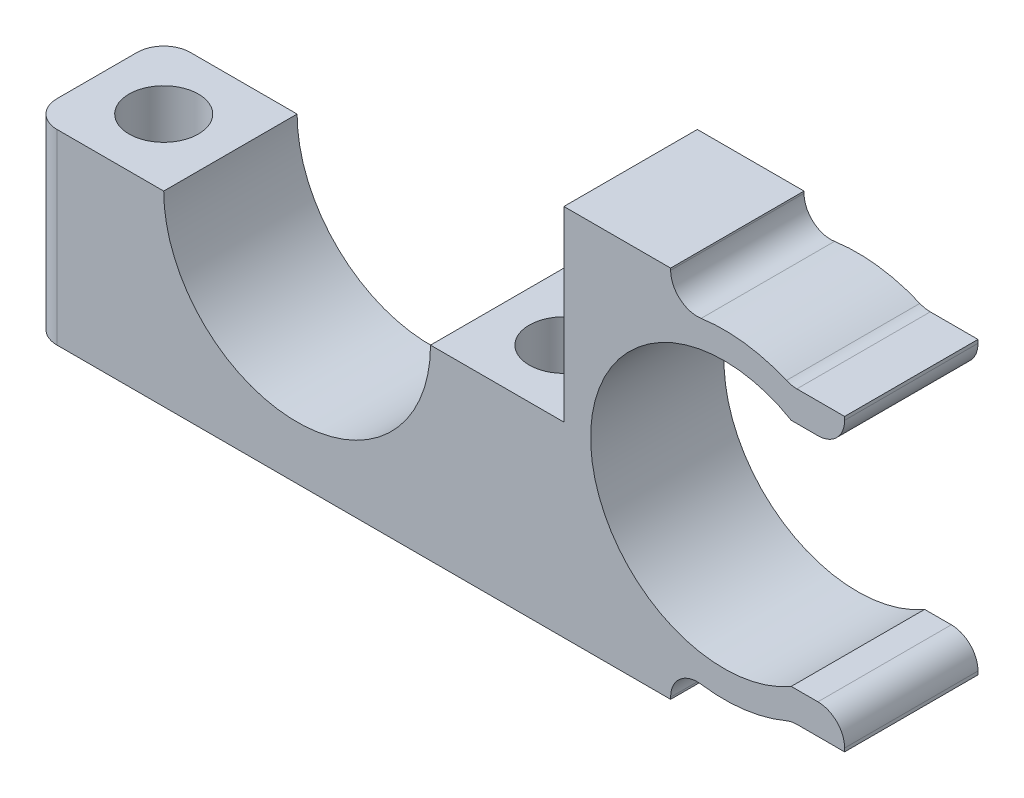
SolidWorks part; units mm, degrees
ref_plane "Front Plane" through (0, 0, 0) normal (0, 0, 1) x (1, 0, 0)
ref_plane "Top Plane" through (0, 0, 0) normal (0, 1, 0) x (1, 0, 0)
ref_plane "Right Plane" through (0, 0, 0) normal (1, 0, 0) x (0, 0, -1)
sketch "Sketch1" plane through (0, 0, 0) normal (0, 0, 1) x (1, 0, 0)
  line L0 (10, 0) -> (20, 0)
  line L1 (20, 0) -> (32, 0) construction
  line L2 (28, -11.3137) -> (28, -14)
  line L3 (20, 14) -> (28, 14)
  line L4 (20, 14) -> (20, 0)
  line L5 (-20, 0) -> (-10, 0)
  line L6 (-20, 0) -> (-20, -14)
  line L7 (-20, -14) -> (20, -14)
  line L8 (20, 0) -> (49, 0) construction
  line L9 (20, -14) -> (28, -14)
  line L10 (28, 14) -> (28, 11.3137)
  line L11 (37.0406, -10.89) -> (37.0406, 10.89) construction
  line L13 (37.0406, 10.89) -> (41.0406, 10.89)
  line L14 (37.0406, 10.89) -> (37.0406, 8.6367) construction
  line L15 (37.0406, 8.6367) -> (41.0406, 8.6367)
  line L16 (41.0406, 10.89) -> (41.0406, 8.6367)
  line L17 (37.0406, -8.6367) -> (41.0406, -8.6367)
  line L18 (37.0406, -8.6367) -> (37.0406, -10.89) construction
  line L19 (37.0406, -10.89) -> (41.0406, -10.89)
  line L20 (41.0406, -8.6367) -> (41.0406, -10.89)
  arc A0 (-10, 0) -> (10, 0) centre (0, 0) ccw
  arc A1 (37.0406, 8.6367) -> (37.0406, -8.6367) centre (32, 0) ccw
  arc A2 (28, -11.3137) -> (37.0406, -10.89) centre (32, 0) ccw
  arc A3 (37.0406, 10.89) -> (28, 11.3137) centre (32, 0) ccw
  dimension "D3" = 20
  dimension "D5" = 20
  dimension "D6" = 24
  dimension "D1" = 12
  dimension "D2" = 40
  dimension "D4" = 14
  dimension "D7" = 28
  dimension "D8" = 8
  dimension "D9" = 4
extrude "Boss-Extrude1" add sketch "Sketch1" along normal blind 10
fillet "Fillet1" radius 2 8 edges at (41.0406, -8.6367, 5) (41.0406, 8.6367, 5) (-20, -7, 0) (-20, -7, 10) (37.0406, 10.89, 5) (37.0406, -10.89, 5) (28, -11.3137, 5) (28, 11.3137, 5)
sketch "Sketch4" plane through (0, 0, 0) normal (0, 1, 0) x (1, 0, 0)
  line L0 (-15, -5) -> (15, -5) construction
  line L1 (0, 0) -> (0, -5) construction
  circle A0 centre (-15, -5) radius 2.6
  circle A1 centre (15, -5) radius 2.6
  point P7 (0, -5)
  dimension "D2" = 5.2
  dimension "D1" = 30
  dimension "D3" = 5
extrude "Cut-Extrude2" cut sketch "Sketch4" against normal through all
